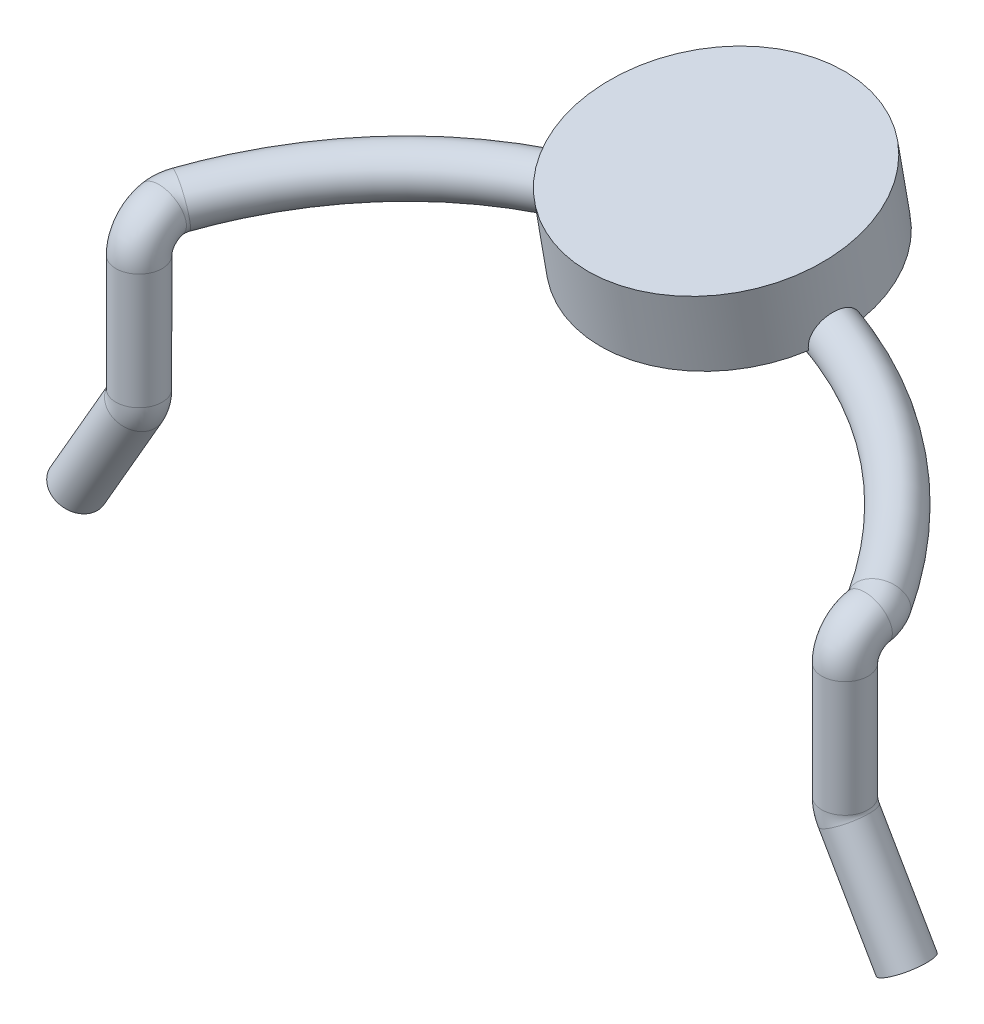
SolidWorks part; units mm, degrees
material "3.0517 (EN-AW 3003)"
ref_plane "Front Plane" through (0, 0, 0) normal (0, 0, 1) x (1, 0, 0)
ref_plane "Top Plane" through (0, 0, 0) normal (0, 1, 0) x (1, 0, 0)
ref_plane "Right Plane" through (0, 0, 0) normal (1, 0, 0) x (0, 0, -1)
sketch "Sketch1" plane through (0, 0, 0) normal (0, 1, 0) x (1, 0, 0)
  line L0 (-6.5, 0) -> (6.5, 0) construction
  circle A0 centre (-6.1, 0) radius 0.4
  circle A1 centre (6.1, 0) radius 0.4
  dimension "D1" = 0.8
  dimension "D2" = 13
extrude "Boss-Extrude1" add sketch "Sketch1" against normal blind 2
sketch "Sketch2" plane through (0, 0, 0) normal (0, 1, 0) x (1, 0, 0)
  line L0 (-6.5, 0.5) -> (6.5, 0.5) construction
  line L1 (0, 0.5) -> (0, 0) construction
  circle A0 centre (6.1, 0) radius 0.4 construction
  circle A1 centre (-6.1, 0) radius 0.4 construction
  circle A2 centre (6.1, 0) radius 0.4
  circle A3 centre (-6.1, 0) radius 0.4
  dimension "D1" = 13
  dimension "D2" = 0.5
revolve "Revolve4" add sketch "Sketch2" angle 80 about L0 reverse direction yes
sketch "Sketch3" plane through (0, 0.0855, -0.4849) normal (0, 0.1736, -0.9848) x (-1, 0, 0)
  line L0 (-6.1, 0.4132) -> (-5.6, 0.4132) construction
  line L1 (-5.6, 0.9106) -> (-5.6, -0.0842) construction
  circle A1 centre (-6.1, 0.4132) radius 0.4
  circle A2 centre (-6.1, 0.4132) radius 0.4
  dimension "D2" = 0.5
  dimension "D1" = 0
revolve "Revolve5" add sketch "Sketch3" angle 30 about L1 reverse direction yes
sketch "Sketch4" plane through (0, 0.0855, -0.4849) normal (0, 0.1736, -0.9848) x (-1, 0, 0)
  line L0 (6.1, 0.4132) -> (5.6, 0.4132) construction
  line L1 (5.6, 0.9666) -> (5.6, -0.1402) construction
  circle A1 centre (6.1, 0.4132) radius 0.4
  circle A2 centre (6.1, 0.4132) radius 0.4
  dimension "D2" = 0.5
  dimension "D1" = 0
revolve "Revolve6" add sketch "Sketch4" angle 30 about L1
ref_point "Point1"
ref_point "Point2"
ref_plane "Plane1" through (0, 0.4069, 0.0717) normal (0, 0.9848, 0.1736) x (1, 0, 0)
sketch "Sketch5" plane through (0, 0.4069, 0.0717) normal (0, 0.9848, 0.1736) x (1, 0, 0)
  line L0 (-5.6866, 0.5424) -> (-6.3794, 0.9424) construction
  line L1 (-5.6866, 0.5424) -> (-6.3794, 0.9424) construction
  line L2 (-6.033, 0.7424) -> (0, 11.1919) construction
  line L3 (6.3794, 0.9424) -> (5.6866, 0.5424) construction
  line L4 (6.3794, 0.9424) -> (5.6866, 0.5424) construction
  line L5 (6.033, 0.7424) -> (0, 11.1919) construction
  arc A0 (-6.033, 0.7424) -> (6.033, 0.7424) centre (0, -2.7408) cw
sketch "Sketch11" plane through (-1.1868, -0.3569, 2.0243) normal (0.5, 0.1504, -0.8529) x (-0.8403, -0.154, -0.5198)
  circle A1 centre (5.3297, 1.7549) radius 0.4
  circle A2 centre (5.3297, 1.7549) radius 0.4
  dimension "D1" = 0
sweep "Sweep1" add profiles "Sketch11" path "Sketch5"
sketch "Sketch12" plane through (0, 0.4069, 0.0717) normal (0, 0.9848, 0.1736) x (1, 0, 0)
  arc A0 (6.033, 0.7424) -> (-6.033, 0.7424) centre (0, -2.7408) ccw construction
  arc A1 (6.033, 0.7424) -> (-6.033, 0.7424) centre (0, -2.7408) ccw construction
  circle A2 centre (0, 4.2256) radius 2.25
  dimension "D1" = 4.5
extrude "Boss-Extrude2" add sketch "Sketch12" along normal blind 1.25
sketch "Sketch13" plane through (0, -2, 0) normal (0, -1, 0) x (1, 0, 0)
  line L0 (6.1, 0) -> (6.6, 0) construction
  line L1 (6.6, -0.2918) -> (6.6, 0.2918) construction
  circle A1 centre (6.1, 0) radius 0.4
  circle A2 centre (6.1, 0) radius 0.4
  dimension "D2" = 0.5
  dimension "D1" = 0
revolve "Revolve7" add sketch "Sketch13" angle 30 about L1
sketch "Sketch14" plane through (2.516, -4.3579, 0) normal (0.5, -0.866, 0) x (0.866, 0.5, 0)
  circle A1 centre (4.2158, 0) radius 0.4
  circle A2 centre (4.2158, 0) radius 0.4
  dimension "D1" = 0
extrude "Boss-Extrude3" add sketch "Sketch14" along normal blind 2
mirror "Mirror1" about plane through (0, 0, 0) normal (1, 0, 0) of "Boss-Extrude3", "Revolve7"
